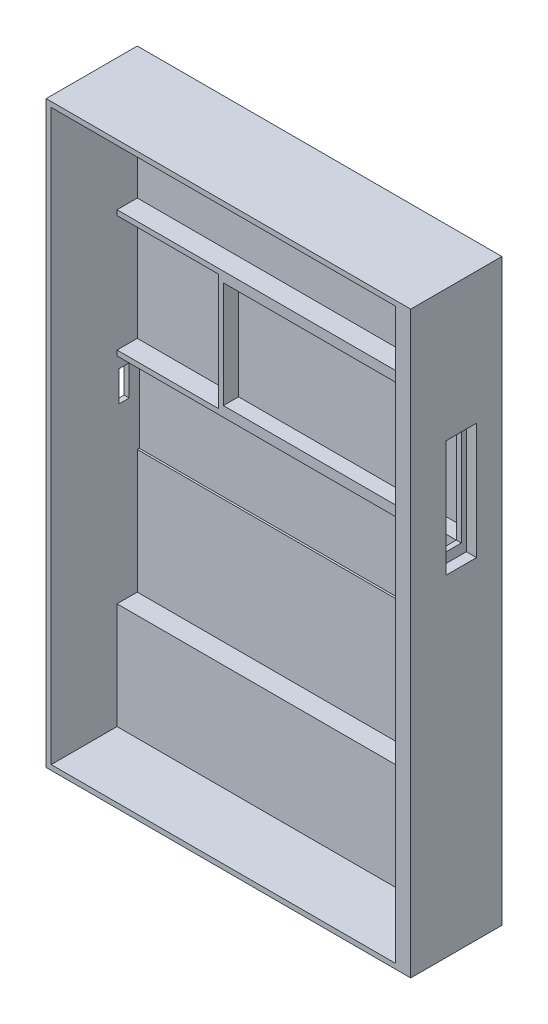
SolidWorks part; units mm, degrees
ref_plane "Přední rovina" through (0, 0, 0) normal (0, 0, 1) x (1, 0, 0)
ref_plane "Horní rovina" through (0, 0, 0) normal (0, 1, 0) x (1, 0, 0)
ref_plane "Pravá rovina" through (0, 0, 0) normal (1, 0, 0) x (0, 0, -1)
sketch "Skica1" plane through (0, 0, 0) normal (0, 0, 1) x (1, 0, 0)
  line L1 (0, 0) -> (55.8, 0)
  line L2 (0, 0) -> (0, 42.4)
  line L3 (0, 42.4) -> (55.8, 42.4)
  line L4 (55.8, 0) -> (55.8, 42.4)
  dimension "D1" = 55.8
  dimension "D2" = 42.4
extrude "Vysunout tenkostěnný1" add sketch "Skica1" along normal blind 18 thin thin type one direction wall 1
extrude "Přidat vysunutím1" add sketch "Skica1<2>" along normal blind 1
sketch "Skica1<2>" plane through (0, 0, 0) normal (0, 0, 1) x (1, 0, 0) same geometry as "Skica1"
sketch "Skica2" plane through (0, 0, 18) normal (0, 0, 1) x (1, 0, 0)
  line L6 (-1, -1) -> (56.8, -1) construction
  line L7 (0, 0) -> (55.8, 0)
  line L8 (0, 0) -> (0, -1)
  line L9 (0, -1) -> (55.8, -1)
  line L10 (55.8, 0) -> (55.8, -1)
  line L13 (55.8, 0) -> (55.8, 42.4) construction
  dimension "D1" = 0
extrude "Odebrat vysunutím3" cut sketch "Skica2" against normal blind 13
sketch "Skica3" plane through (-1, 0, 0) normal (-1, 0, 0) x (0, 0, 1)
  line L1 (4.6, 40) -> (2.6, 40)
  line L2 (4.6, 40) -> (4.6, 34)
  line L3 (4.6, 34) -> (2.6, 34)
  line L4 (2.6, 40) -> (2.6, 34)
  line L5 (5, 0) -> (1, 0) construction
  line L9 (1, 42.4) -> (1, 0) construction
  dimension "D1" = 34
  dimension "D2" = 1.6
  dimension "D3" = 6
  dimension "D4" = 2
extrude "Odebrat vysunutím4" cut sketch "Skica3" against normal blind 10
sketch "Skica4" plane through (0, 0, 1) normal (0, 0, 1) x (1, 0, 0)
  line L0 (55.8, -1) -> (55.8, 42.4) construction
  line L1 (0, 42.4) -> (55.8, 42.4)
  line L2 (0, 42.4) -> (0, 24.4)
  line L3 (0, 24.4) -> (55.8, 24.4)
  line L4 (55.8, 42.4) -> (55.8, 24.4)
  line L5 (0, 0) -> (55.8, 0) construction
  dimension "D1" = 24.4
extrude "Odebrat vysunutím5" cut sketch "Skica4" against normal blind 0.4
sketch "Skica5" plane through (0, 0, 0) normal (0, 0, 1) x (1, 0, 0)
  line L6 (56.8, 43.4) -> (-1, 43.4) construction
  line L7 (0, 43.4) -> (20, 43.4)
  line L8 (0, 43.4) -> (0, 66.4)
  line L9 (0, 66.4) -> (20, 66.4)
  line L10 (20, 43.4) -> (20, 66.4)
  line L13 (0, 42.4) -> (0, 24.4) construction
  dimension "D1" = 0
  dimension "D2" = 23
  dimension "D3" = 20
extrude "Vysunout tenkostěnný2" add sketch "Skica5" along normal blind 18 thin thin type one direction wall 1
extrude "Přidat vysunutím2" add sketch "Skica5<2>" along normal blind 1
sketch "Skica5<2>" plane through (0, 0, 0) normal (0, 0, 1) x (1, 0, 0) same geometry as "Skica5"
sketch "Skica7" plane through (0, 0, 0) normal (0, 0, 1) x (1, 0, 0)
  line L0 (21, 43.4) -> (21, 67.4) construction
  line L5 (21, 65.4) -> (67, 65.4)
  line L6 (21, 65.4) -> (21, 44.4)
  line L7 (21, 44.4) -> (67, 44.4)
  line L8 (67, 65.4) -> (67, 44.4)
  line L14 (21, 67.4) -> (-1, 67.4) construction
  dimension "D1" = 46
  dimension "D2" = 2
  dimension "D3" = 21
extrude "Vysunout tenkostěnný3" add sketch "Skica7" along normal blind 18 thin thin type one direction wall 1
extrude "Přidat vysunutím3" add sketch "Skica7<2>" along normal blind 2
sketch "Skica7<2>" plane through (0, 0, 0) normal (0, 0, 1) x (1, 0, 0) same geometry as "Skica7"
sketch "Skica8" plane through (0, 0, 0) normal (0, 0, 1) x (1, 0, 0)
  line L1 (0, 67.4) -> (68, 67.4)
  line L2 (0, 67.4) -> (0, 91.4)
  line L3 (0, 91.4) -> (68, 91.4)
  line L4 (68, 67.4) -> (68, 91.4)
  line L5 (21, 67.4) -> (-1, 67.4) construction
  line L8 (0, 66.4) -> (0, 43.4) construction
  dimension "D1" = 0
  dimension "D2" = 0
  dimension "D3" = 68
  dimension "D4" = 24
extrude "Přidat vysunutím4" add sketch "Skica8" along normal blind 1
extrude "Vysunout tenkostěnný4" add sketch "Skica8<2>" along normal blind 18 thin thin type one direction wall 1
sketch "Skica8<2>" plane through (0, 0, 0) normal (0, 0, 1) x (1, 0, 0) same geometry as "Skica8"
sketch "Skica9" plane through (0, 0, 0) normal (0, 0, 1) x (1, 0, 0)
  line L1 (71, 92.4) -> (71, -1)
  line L2 (71, -1) -> (56.8, -1)
  line L8 (55.8, -1) -> (56.8, -1) construction
  line L9 (68, 43.4) -> (68, 92.4)
  line L10 (68, 92.4) -> (71, 92.4)
  line L11 (69, 92.4) -> (-1, 92.4) construction
  line L14 (56.8, 43.4) -> (56.8, -1)
  line L26 (68, 43.4) -> (56.8, 43.4)
  dimension "D1" = 0
  dimension "D2" = 14.2
extrude "Přidat vysunutím5" add sketch "Skica9" along normal blind 18
sketch "Skica10" plane through (71, 0, 0) normal (1, 0, 0) x (0, 0, -1)
  line L0 (-18, 42.4) -> (-0.6, 42.4) construction
  line L1 (-11, 66.4) -> (-5, 66.4)
  line L2 (-11, 66.4) -> (-11, 43.4)
  line L3 (-11, 43.4) -> (-5, 43.4)
  line L4 (-5, 66.4) -> (-5, 43.4)
  line L6 (-18, 65.4) -> (-2, 65.4) construction
  line L7 (-2, 44.4) -> (-2, 65.4) construction
  dimension "D1" = 3
  dimension "D2" = 6
  dimension "D3" = 1
  dimension "D4" = 1
extrude "Odebrat vysunutím7" cut sketch "Skica10" against normal blind 2
sketch "Skica15" plane through (0, 42.4, 0) normal (0, -1, 0) x (1, 0, 0)
  line L0 (55.8, 5) -> (55.8, 18) construction
  line L1 (0, 18) -> (55.8, 18)
  line L2 (0, 18) -> (0, 5)
  line L3 (0, 5) -> (55.8, 5)
  line L4 (55.8, 18) -> (55.8, 5)
  line L6 (0, 1) -> (20, 1) construction
  dimension "D1" = 4
extrude "Odebrat vysunutím13" cut sketch "Skica15" against normal blind 40
sketch "Skica17" plane through (0, 0, 0) normal (0, 0, 1) x (1, 0, 0)
  line L1 (0, -1) -> (68, -1)
  line L2 (0, -1) -> (0, -21)
  line L3 (0, -21) -> (68, -21)
  line L4 (68, -1) -> (68, -21)
  line L6 (0, -1) -> (55.8, -1) construction
  line L8 (68, 67.4) -> (68, 91.4) construction
  line L9 (0, 42.4) -> (0, 24.4) construction
  dimension "D1" = 0
  dimension "D2" = 0
  dimension "D3" = 20
  dimension "D4" = 0
extrude "Přidat vysunutím6" add sketch "Skica17" along normal blind 5
sketch "Skica18" plane through (0, 0, 0) normal (0, 0, 1) x (1, 0, 0)
  line L2 (-1, -22) -> (71, -22)
  line L3 (71, -22) -> (71, -1)
  line L8 (71, -1) -> (55.8, -1)
  line L9 (55.8, -1) -> (55.8, -21)
  line L11 (55.8, -21) -> (0, -21)
  line L16 (-1, -22) -> (-1, -1)
  line L17 (-1, -1) -> (0, -1)
  line L18 (0, -1) -> (0, -21)
  line L20 (0, 24.4) -> (0, 0) construction
  line L21 (-1, -1) -> (0, -1) construction
  line L23 (0, -21) -> (68, -21) construction
  line L24 (71, -1) -> (71, 92.4) construction
  line L25 (55.8, 0) -> (55.8, 24.4) construction
  dimension "D1" = 0
  dimension "D2" = 0
  dimension "D3" = 0
  dimension "D4" = 1
  dimension "D5" = 1
  dimension "D6" = 0
  dimension "D7" = 0
extrude "Přidat vysunutím7" add sketch "Skica18" along normal blind 18
sketch "Skica16" plane through (0, 65.4, 0) normal (0, -1, 0) x (1, 0, 0)
  line L1 (55.8, 18) -> (68, 18)
  line L2 (55.8, 18) -> (55.8, 5)
  line L3 (55.8, 5) -> (68, 5)
  line L4 (68, 18) -> (68, 5)
  line L7 (67, 2) -> (21, 2) construction
  line L8 (68, 18) -> (68, 1) construction
  dimension "D1" = 0
  dimension "D2" = 3
extrude "Odebrat vysunutím14" cut sketch "Skica16" against normal blind 10 and the other way blind 86.4
sketch "Skica19" plane through (69, 0, 0) normal (1, 0, 0) x (0, 0, -1)
  line L0 (-5, 66.4) -> (-11, 66.4) construction
  line L1 (-10, 65.4) -> (-6, 65.4)
  line L2 (-10, 65.4) -> (-10, 45.4)
  line L3 (-10, 45.4) -> (-6, 45.4)
  line L4 (-6, 65.4) -> (-6, 45.4)
  line L5 (-5, 43.4) -> (-5, 66.4) construction
  line L6 (-11, 43.4) -> (-5, 43.4) construction
  line L7 (-11, 66.4) -> (-11, 43.4) construction
  dimension "D1" = 1
  dimension "D2" = 1
  dimension "D3" = 2
  dimension "D4" = 1
extrude "Odebrat vysunutím15" cut sketch "Skica19" against normal blind 2
